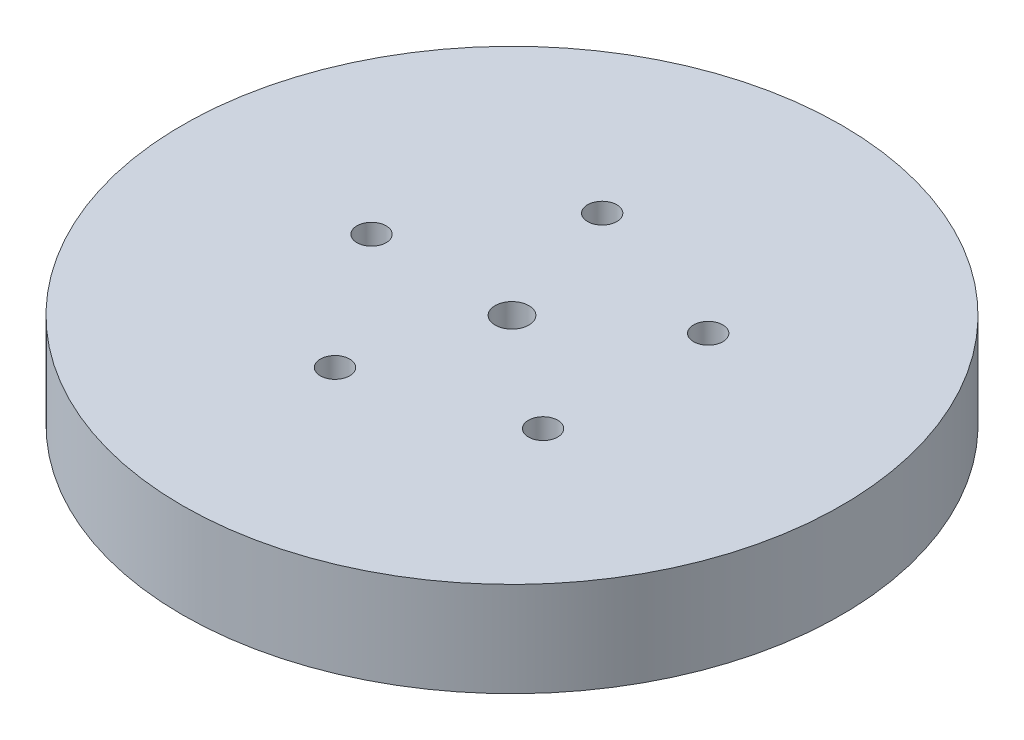
SolidWorks part; units mm, degrees
ref_plane "Front Plane" through (0, 0, 0) normal (0, 0, 1) x (1, 0, 0)
ref_plane "Top Plane" through (0, 0, 0) normal (0, 1, 0) x (1, 0, 0)
ref_plane "Right Plane" through (0, 0, 0) normal (1, 0, 0) x (0, 0, -1)
sketch "Sketch1" plane through (0, 0, 0) normal (0, 1, 0) x (1, 0, 0)
  circle A0 centre (0, 0) radius 97.5
  dimension "FLANGE_OD" = 195
extrude "Boss-Extrude1" add sketch "Sketch1" along normal blind 28
sketch "Sketch2" plane through (0, 0, 0) normal (0, 1, 0) x (1, 0, 0)
  circle A0 centre (0, 0) radius 5
  dimension "BORE_D" = 10
extrude "Cut-Extrude1" cut sketch "Sketch2" along normal through all
sketch "Sketch3" plane through (0, 28, 0) normal (0, 1, 0) x (1, 0, 0)
  circle A0 centre (0, 0) radius 41.5576 construction
  circle A1 centre (-41.5576, 0) radius 4.3266
  dimension "BOLT_D" = 8.6531
  dimension "BOLT_PCD" = 83.1151
extrude "Cut-Extrude2" cut sketch "Sketch3" against normal blind 16.8074
pattern_circular "CirPattern1" count 5 over 360 about axis through (0, 0, 0) along (0, 1, 0) of "Cut-Extrude2"
